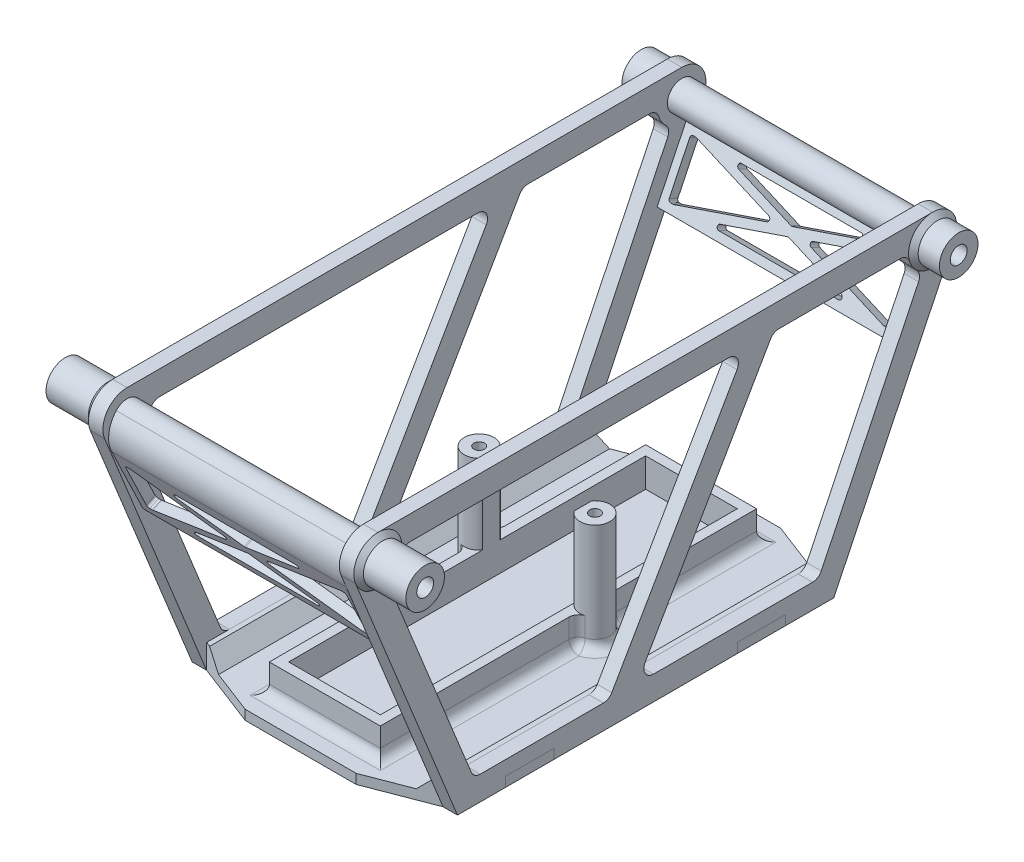
SolidWorks part; units mm, degrees
note: The reader was unsure of these and kept them because the rebuilt part matched: shared geometry of "Motor Box Sketch<3>", "Sketch6<3>".
other "Base Plate"
other "Left Wall"
other "Right Wall" parameters "Right Wall Plane"=27.5, "D5"=6.6366, "Joint Hole"=2.3, "D1"=14.5895, "D2"=39.8474, "D3"=19.0477, "D4"=55.6971, "D6"=33.5359, "D7"=45.542, "Wall Width"=5, "Notch Width"=10, "D8"=2.3856, "Notch Height"=2, "D9"=11.0795, "Bottom Notch From Edge"=10, "Screw Hole Diameter"=2.2, "Motor Box Length"=74, "Motor Box Width"=19, "Screw Hole Centre from Motor Rear"=20, "Screw Hole Spacing"=24, "Screw Hole Wall Thickness"=2, "Motor Rear to Shaft Centre"=12.5, "Motor Length"=74, "Motor Width"=19, "Motor Wall Thickness"=2, "IDK"=0, "Motor Shaft Above Base"=14, "Front Riser"=9.8, "Rear Riser"=5.4, "Edge Chamfer Width"=4
material "ABS"
ref_plane "Front Plane" through (0, 0, 0) normal (0, 0, 1) x (1, 0, 0)
ref_plane "Top Plane" through (0, 0, 0) normal (0, 1, 0) x (1, 0, 0)
ref_plane "Right Plane" through (0, 0, 0) normal (1, 0, 0) x (0, 0, -1)
sketch "Motor Box Sketch" plane through (0, 0, 0) normal (0, 1, 0) x (1, 0, 0)
  line L0 (-11.5, 14.5) -> (11.5, 14.5)
  line L1 (-9.5, -61.5) -> (9.5, -61.5)
  line L2 (-9.5, -61.5) -> (-9.5, 12.5)
  line L3 (-9.5, 12.5) -> (9.5, 12.5)
  line L4 (9.5, -61.5) -> (9.5, 12.5)
  line L5 (-9.5, -61.5) -> (9.5, 12.5) construction
  line L6 (-9.5, 12.5) -> (9.5, -61.5) construction
  line L7 (11.5, -63.5) -> (11.5, -22.5594)
  line L8 (-11.5, -63.5) -> (11.5, -63.5)
  line L9 (-11.5, -63.5) -> (-11.5, -22.5594)
  line L10 (-12, -19.5) -> (12, -19.5) construction
  line L11 (0, -24.5) -> (0, -19.5) construction
  line L12 (-11.5, -16.4406) -> (-11.5, 14.5)
  line L13 (-11.5, -63.5) -> (-11.5, 14.5) construction
  line L14 (11.5, -16.4406) -> (11.5, 14.5)
  line L15 (11.5, -63.5) -> (11.5, 14.5) construction
  line L16 (-9.5, -61.5) -> (-9.5, 12.5)
  line L17 (-9.5, -61.5) -> (9.5, -61.5)
  line L18 (-9.5, 12.5) -> (9.5, -61.5) construction
  circle A0 centre (-12, -19.5) radius 1.1
  circle A1 centre (12, -19.5) radius 1.1
  arc A2 (-11.5, -16.4406) -> (-11.5, -22.5594) centre (-12, -19.5) ccw
  arc A3 (11.5, -16.4406) -> (11.5, -22.5594) centre (12, -19.5) cw
  arc A6 (11.5, -16.4406) -> (11.5, -22.5594) centre (12, -19.5) ccw
  arc A8 (-11.5, -16.4406) -> (-11.5, -22.5594) centre (-12, -19.5) cw
  dimension "Screw Hole Centre from Motor Rear" = 19.5
extrude "Motor Box Extrude" add sketch "Motor Box Sketch" along normal blind 8 from offset 14 offset against normal yes
extrude "Motor Riser Extrude" add sketch "Motor Box Sketch<3>" along normal blind 24.5 from surface at -14 contours A3 A6 L4 A1 | A8 A2 L16 A0
sketch "Motor Box Sketch<3>" plane through (0, 0, 0) normal (0, 1, 0) x (1, 0, 0) same geometry as "Motor Box Sketch"
ref_plane "Right Wall" through (-27.5, 0, 0) normal (1, 0, 0) x (0, 0, -1)
sketch "Right Wall Sketch" plane through (-27.5, 0, 0) normal (1, 0, 0) x (0, 0, -1)
  line L0 (35, 45) -> (-80, 45)
  line L1 (22.0941, 13.2483) -> (26.5974, 11.0758) construction
  line L2 (32.8274, 35.4967) -> (11.3607, -9)
  line L3 (-17.9527, 15.5) -> (-13.6226, 13) construction
  line L6 (1.9658, 40) -> (30, 40)
  line L7 (14.5, -14) -> (4.5, -14)
  line L8 (14.5, -6) -> (14.5, -14) construction
  line L9 (-63.5, -6) -> (-63.5, -14) construction
  line L10 (-63.5, -14) -> (-84.6336, 38.1212)
  line L11 (14.5, -14) -> (39.5033, 37.8274)
  line L13 (11.3607, -9) -> (-26.3243, -9)
  line L14 (-26.3243, -9) -> (1.9658, 40)
  line L15 (-75, 40) -> (-3.8077, 40)
  line L17 (-60.132, -9) -> (-78.1212, 35.3664)
  line L18 (-69.1266, 13.1832) -> (-73.7602, 11.3044) construction
  line L19 (-24.5, -14) -> (-24.5, -9) construction
  line L20 (-5.5, -12) -> (-24.5, -12) construction
  line L24 (1.9658, 40) -> (-3.8077, 40) construction
  line L25 (-39.4038, 40) -> (-39.4038, 45) construction
  line L27 (4.5, -14) -> (4.5, -12)
  line L28 (4.5, -12) -> (-5.5, -12)
  line L29 (-5.5, -12) -> (-5.5, -14)
  line L30 (-43.5, -14) -> (-43.5, -12)
  line L31 (-43.5, -12) -> (-53.5, -12)
  line L32 (-53.5, -12) -> (-53.5, -14)
  line L33 (-24.5, -12) -> (-43.5, -12) construction
  line L34 (-5.5, -14) -> (-43.5, -14)
  line L35 (-53.5, -14) -> (-63.5, -14)
  line L36 (-60.132, -9) -> (-32.0978, -9)
  line L37 (-22.6, -14) -> (-16.4, -14) construction
  line L38 (-32.0978, -9) -> (-3.8077, 40)
  line L39 (-16.4406, -14) -> (14.5, -14) construction
  circle A0 centre (35, 40) radius 1.15
  circle A1 centre (-80, 40) radius 1.15
  arc A2 (39.5033, 37.8274) -> (35, 45) centre (35, 40) ccw
  arc A3 (-80, 45) -> (-84.6336, 38.1212) centre (-80, 40) ccw
  arc A4 (-75, 40) -> (-78.1212, 35.3664) centre (-80, 40) cw
  arc A5 (30, 40) -> (32.8274, 35.4967) centre (35, 40) ccw
  arc A6 (39.5033, 37.8274) -> (32.8274, 35.4967) centre (35, 40) cw construction
  arc A7 (-84.6336, 38.1212) -> (-78.1212, 35.3664) centre (-80, 40) ccw construction
  point P54 (-17.9527, 15.5)
  dimension "D1" = 35
  dimension "D2" = 40
  dimension "D3" = 40
  dimension "D4" = 80
  dimension "D6" = 60
  dimension "D7" = 2
extrude "Right Wall Extrude" add sketch "Right Wall Sketch" along normal blind 3 separate body
sketch "Sketch6" plane through (-27.5, 0, 0) normal (-1, 0, 0) x (0, 0, 1)
  circle A0 centre (-35, 40) radius 4
  circle A1 centre (80, 40) radius 4
  circle A3 centre (-35, 40) radius 1.75
  circle A4 centre (80, 40) radius 1.75
  circle M24 centre (-35, 40) radius 1.15
  circle M25 centre (80, 40) radius 1.15
  dimension "D1" = 2.25
  dimension "Threaded Insert Hole" = 3.5
extrude "Front Joint Riser Extrude" add sketch "Sketch6" along normal blind 9.8 contours A1 M25
extrude "Rear Joint Riser Extrude" add sketch "Sketch6<3>" along normal blind 5.4 contours A0 M24
sketch "Sketch6<3>" plane through (-27.5, 0, 0) normal (-1, 0, 0) x (0, 0, 1) same geometry as "Sketch6"
fillet "Right Wall Fillet" radius 2 10 edges at (-26, 35.3664, 78.1212) (-26, 40, 75) (-26, 40, -1.9658) (-26, 35.4967, -32.8274) (-26, 40, -30) (-26, -9, -11.3607) (-26, -9, 26.3243) (-26, 40, 3.8077) (-26, -9, 60.132) (-26, -9, 32.0978)
chamfer "Riser Fillet" distance 1 angle 45 2 edges at (-27.5, 40, 76) (-27.5, 40, -39)
mirror "Left Wall Mirror" about plane through (0, 0, 0) normal (1, 0, 0) of bodies 107 102
sketch "Bottom Plate Sketch" plane through (0, -14, 0) normal (0, -1, 0) x (1, 0, 0)
  line L12 (24.5, -4.5) -> (24.5, -14.5) construction
  line L13 (24.5, -4.5) -> (27.5, -4.5) construction
  line L14 (27.5, 5.5) -> (27.5, -4.5) construction
  line L15 (24.5, 5.5) -> (27.5, 5.5) construction
  line L16 (24.5, 43.5) -> (24.5, 5.5) construction
  line L17 (24.5, 43.5) -> (27.5, 43.5) construction
  line L18 (27.5, 53.5) -> (27.5, 43.5) construction
  line L19 (24.5, 53.5) -> (27.5, 53.5) construction
  line L20 (24.5, 63.5) -> (24.5, 53.5) construction
  line L21 (-24.5, 63.5) -> (-24.5, 53.5) construction
  line L22 (-24.5, 53.5) -> (-27.5, 53.5) construction
  line L23 (-27.5, 53.5) -> (-27.5, 43.5) construction
  line L24 (-24.5, 43.5) -> (-27.5, 43.5) construction
  line L25 (-24.5, 43.5) -> (-24.5, 5.5) construction
  line L26 (-24.5, 5.5) -> (-27.5, 5.5) construction
  line L27 (-27.5, 5.5) -> (-27.5, -4.5) construction
  line L28 (-24.5, -4.5) -> (-27.5, -4.5) construction
  line L29 (-24.5, -4.5) -> (-24.5, -14.5) construction
  line L30 (24.5, -4.5) -> (24.5, -14.5)
  line L31 (24.5, -4.5) -> (27.5, -4.5)
  line L32 (27.5, 5.5) -> (27.5, -4.5)
  line L33 (24.5, 5.5) -> (27.5, 5.5)
  line L34 (24.5, 43.5) -> (24.5, 5.5)
  line L35 (24.5, 43.5) -> (27.5, 43.5)
  line L36 (27.5, 53.5) -> (27.5, 43.5)
  line L37 (24.5, 53.5) -> (27.5, 53.5)
  line L38 (24.5, 63.5) -> (24.5, 53.5)
  line L39 (-24.5, 63.5) -> (-24.5, 53.5)
  line L40 (-24.5, 53.5) -> (-27.5, 53.5)
  line L41 (-27.5, 53.5) -> (-27.5, 43.5)
  line L42 (-24.5, 43.5) -> (-27.5, 43.5)
  line L43 (-24.5, 43.5) -> (-24.5, 5.5)
  line L44 (-24.5, 5.5) -> (-27.5, 5.5)
  line L45 (-27.5, 5.5) -> (-27.5, -4.5)
  line L46 (-24.5, -4.5) -> (-27.5, -4.5)
  line L47 (-24.5, -4.5) -> (-24.5, -14.5)
  line L48 (-24.5, 63.5) -> (-11.5, 68.5)
  line L49 (-11.5, 68.5) -> (11.5, 68.5)
  line L50 (11.5, 68.5) -> (24.5, 63.5)
  line L51 (-24.5, -14.5) -> (-11.5, -19.5)
  line L52 (-11.5, -19.5) -> (11.5, -19.5)
  line L53 (11.5, -19.5) -> (24.5, -14.5)
  line L54 (0, 63.5) -> (0, 68.5) construction
  line L55 (0, -19.5) -> (0, -14.5) construction
  line L56 (-11.5, -14.5) -> (11.5, -14.5) construction
  line L57 (-11.5, 63.5) -> (11.5, 63.5) construction
  line L58 (-11.5, -14.5) -> (11.5, -14.5) construction
  line L59 (-11.5, 63.5) -> (11.5, 63.5) construction
  dimension "D1" = 5
extrude "Bottom Plate Extrude" add sketch "Bottom Plate Sketch" against normal blind 2
fillet "Box Fillet" radius 2 12 edges at (11.5, -9, 16.4406) (11.5, -9, 22.5594) (-11.5, -9, 22.5594) (-11.5, -9, 16.4406) (-11.5, -12, 0.9703) (0, -12, -14.5) (11.5, -12, 0.9703) (15.1, -12, 19.5) (-15.1, -12, 19.5) (-11.5, -12, 43.0297) (11.5, -12, 43.0297) (0, -12, 63.5)
sketch "Sketch7" plane through (0, -12, 0) normal (0, 1, 0) x (1, 0, 0)
  line L0 (-20.5, 16.0385) -> (-20.5, -65.0385)
  line L1 (-24.5, 14.5) -> (-11.5, 19.5) construction
  line L2 (-11.5, -68.5) -> (-24.5, -63.5) construction
  line L3 (20.5, -65.0385) -> (20.5, 16.0385)
  line L4 (24.5, -63.5) -> (11.5, -68.5) construction
  line L5 (11.5, 19.5) -> (24.5, 14.5) construction
  line L6 (-24.5, -43.5) -> (-24.5, -5.5) construction
  line L7 (20.5, -24.5) -> (24.5, -24.5) construction
  line L8 (24.5, -5.5) -> (24.5, -43.5) construction
  line L9 (-20.5, -24.5) -> (-24.5, -24.5) construction
  line L10 (20.5, 16.0385) -> (24.5, 14.5)
  line L11 (24.5, -63.5) -> (11.5, -68.5)
  line L12 (-11.5, -68.5) -> (-24.5, -63.5)
  line L13 (-24.5, 14.5) -> (-20.5, 16.0385)
  line L14 (-24.5, 14.5) -> (-24.5, -63.5)
  line L15 (24.5, 14.5) -> (24.5, -63.5)
  line M13 (24.5, 4.5) -> (24.5, 14.5)
  line M14 (24.5, 14.5) -> (11.5, 19.5)
  line M16 (-11.5, 19.5) -> (-24.5, 14.5)
  line M17 (-24.5, 14.5) -> (-24.5, 4.5)
  line M21 (-24.5, -5.5) -> (-24.5, -43.5)
  line M25 (-24.5, -53.5) -> (-24.5, -63.5)
  line M26 (-24.5, -63.5) -> (-11.5, -68.5)
  line M28 (11.5, -68.5) -> (24.5, -63.5)
  line M29 (24.5, -63.5) -> (24.5, -53.5)
  line M33 (24.5, -43.5) -> (24.5, -5.5)
extrude "Base Plate Chamfer Extrude" add sketch "Sketch7" along normal blind 3 contours L15 L3 M13 M14 M28 M29 M33 | L14 L0 M17 M21 M25 M26 M16
chamfer "Base Plate Chamfer" distance 3 angle 45 2 edges at (-20.5, -9, 24.5) (20.5, -9, 24.5)
sketch "Sketch8" plane through (-24.5, 0, 0) normal (1, 0, 0) x (0, 0, -1)
  line L0 (14.5, -14) -> (39.5033, 37.8274) construction
  line L2 (31.6821, 21.6155) -> (38.1998, 35.1254)
  line L3 (29.8808, 22.4845) -> (36.3985, 35.9945)
  line L4 (31.6821, 21.6155) -> (29.8808, 22.4845)
  line L6 (36.3985, 35.9945) -> (33.6965, 37.298)
  line L7 (36.3985, 35.9945) -> (38.1998, 35.1254) construction
  circle A0 centre (35, 40) radius 1.15 construction
  circle A2 centre (35, 40) radius 1.15
  arc A5 (37.2425, 41.9928) -> (33.6965, 37.298) centre (35, 40) ccw
  arc A6 (38.1998, 35.1254) -> (37.2425, 41.9928) centre (32.5706, 37.8411) ccw
  circle M4 centre (35, 40) radius 1.15
  line M18 (14.5, -14) -> (39.5033, 37.8274)
  dimension "D2" = 15
  dimension "D3" = 3
  dimension "D1" = 2
extrude "Boss-Extrude1" add sketch "Sketch8" along direction (-1, 0, 0) on the side of the normal up to surface (49 mm away) separate body contours L6 L7 A6 A5 M4 | L7 L3 L4 M18 up to face at (24.5, 40, -36.15)
fillet "Fillet1" radius 1 1 edges at (0, 35.9945, -36.3985)
sketch "Sketch9" plane through (0, -7.4488, -15.44) normal (0, 0.4345, 0.9007) x (1, 0, 0)
  line L0 (24.2802, 48.0038) -> (-25.6127, 33.7487) construction
  line L1 (24.7198, 46.4653) -> (-25.1731, 32.2102) construction
  line L2 (-24.2802, 48.0038) -> (25.9696, 33.6467) construction
  line L3 (-24.7198, 46.4653) -> (25.53, 32.1083) construction
  line L9 (15.988, 45.6346) -> (-15.988, 45.6346)
  line L11 (-22.9, 34.8346) -> (-22.9, 45.6346)
  line L20 (-24.5, 47.2346) -> (24.5, 33.2346) construction
  line L21 (24.5, 47.2346) -> (-24.5, 33.2346) construction
  line L22 (-21.812, 45.6346) -> (-2.912, 40.2346)
  line L23 (15.988, 45.6346) -> (0, 41.0666)
  line L24 (-15.988, 45.6346) -> (0, 41.0666)
  line L25 (21.812, 45.6346) -> (2.912, 40.2346)
  line L30 (0, 39.4026) -> (15.988, 34.8346)
  line L31 (2.912, 40.2346) -> (21.812, 34.8346)
  line L32 (0, 39.4026) -> (-15.988, 34.8346)
  line L33 (-2.912, 40.2346) -> (-21.812, 34.8346)
  line L34 (21.812, 45.6346) -> (22.9, 45.6346)
  line L35 (24.5, 47.2346) -> (-24.5, 47.2346) construction
  line L36 (24.5, 47.2346) -> (-24.5, 47.2346)
  line L37 (-24.5, 33.2346) -> (-24.5, 47.2346) construction
  line L38 (24.5, 33.2346) -> (-24.5, 33.2346) construction
  line L39 (24.5, 47.2346) -> (24.5, 33.2346) construction
  line L40 (-24.5, 33.2346) -> (-24.5, 47.2346)
  line L41 (24.5, 33.2346) -> (-24.5, 33.2346)
  line L42 (24.5, 47.2346) -> (24.5, 33.2346)
  line L43 (24.5, 47.2346) -> (-25.3929, 32.9795) construction
  line L44 (-24.5, 47.2346) -> (25.7498, 32.8775) construction
  line L45 (22.9, 34.8346) -> (21.812, 34.8346)
  line L46 (22.9, 45.6346) -> (22.9, 34.8346)
  line L47 (-21.812, 45.6346) -> (-22.9, 45.6346)
  line L48 (22.9, 45.6346) -> (-22.9, 45.6346) construction
  line L49 (-21.812, 34.8346) -> (-22.9, 34.8346)
  line L50 (22.9, 34.8346) -> (-22.9, 34.8346) construction
  line L51 (15.988, 34.8346) -> (-15.988, 34.8346)
  dimension "D1" = 1.6
  dimension "D2" = 0.8
  dimension "D3" = 0.8
extrude "Cut-Extrude1" cut sketch "Sketch9" against normal blind 10
fillet "Fillet2" radius 0.5 15 edges at (0, 27.6053, -33.4615) (2.912, 28.3546, -33.823) (15.988, 23.491, -31.4767) (21.812, 23.491, -31.4767) (22.9, 23.491, -31.4767) (0, 29.104, -34.1846) (22.9, 33.2182, -36.1694) (15.988, 33.2182, -36.1694) (-15.988, 33.2182, -36.1694) (-15.988, 23.491, -31.4767) (-2.912, 28.3546, -33.823) (-21.812, 23.491, -31.4767) (-22.9, 23.491, -31.4767) (-21.812, 33.2182, -36.1694) (-22.9, 33.2182, -36.1694)
sketch "Sketch10" plane through (0, 0, 0) normal (1, 0, 0) x (0, 0, -1)
  line L0 (35, 40) -> (-80, 40) construction
  circle A0 centre (35, 40) radius 1.15 construction
  circle A1 centre (-80, 40) radius 1.15 construction
  circle A2 centre (35, 40) radius 1.15 construction
  circle A3 centre (-80, 40) radius 1.15 construction
  point P6 (-22.5, 40)
ref_plane "Plane1" through (0, 0, 22.5) normal (0, 0, 1) x (1, 0, 0)
mirror "Mirror1" about plane through (0, 0, 22.5) normal (0, 0, 1) of bodies 114
equation "\"Overall Width\"= 55"
equation "\"Rear Ground X\"= 35"
equation "\"Rear Ground Y\"= 40"
equation "\"Front Ground X\"= 80"
equation "\"Front Ground Y\"= 40"
equation "\"Right Wall Plane@Right Wall\" = \"Overall Width\" / 2"
equation "\"D1@Right Wall Sketch\" = \"Rear Ground X\""
equation "\"D2@Right Wall Sketch\" = \"Rear Ground Y\""
equation "\"D3@Right Wall Sketch\" = \"Front Ground Y\""
equation "\"D4@Right Wall Sketch\" = \"Front Ground X\""
equation "\"Joint Hole Diameter\"= 2.3"
equation "\"Joint Hole@Right Wall Sketch\" = \"Joint Hole Diameter\""
equation "\"Notch Width\"=10"
equation "\"Notch Height\"=2"
equation "\"Bottom Notch From Edge@Right Wall Sketch\" = \"Notch Width\""
equation "\"D1@Bottom Plate Extrude\" = \"Notch Height\""
equation "\"Motor Shaft Height\"= 12"
equation "\"Motor Shaft from End\"= 12.5"
equation "\"Motor Rear to Shaft Centre@Motor Box Sketch\"= \"Motor Shaft from End\""
equation "\"Motor Shaft Above Base@Motor Box Extrude\"= \"Motor Shaft Height\" + \"Base Plate Thickness\""
equation "\"Motor Riser Height\"= 22.5"
equation "\"D1@Motor Riser Extrude\" = \"Motor Riser Height\" + \"Base Plate Thickness\""
equation "\"Base Plate Thickness\"= 2"
equation "\"Screw Hole from Shaft\"= 19.5"
equation "\"Screw Hole Centre from Motor Rear@Motor Box Sketch\"=\"Screw Hole from Shaft\""
equation "\"Front Linkage Riser\"= 9.8"
equation "\"Rear Linkage Riser\"= 5.4"
equation "\"Front Riser@Front Joint Riser Extrude\"= \"Front Linkage Riser\""
equation "\"Rear Riser@Rear Joint Riser Extrude\"= \"Rear Linkage Riser\""
equation "\"D7@Right Wall Sketch\"=\"Notch Height\""
equation "\"Base Plate Edge Chamfer Height\"= 3"
equation "\"Edge Chamfer Width@Sketch7\" = \"Base Plate Edge Chamfer Height\" + 1"
equation "\"D1@Base Plate Chamfer Extrude\" = \"Base Plate Edge Chamfer Height\""
equation "\"D3@LPattern1\"=\"Rear Ground X\"+\"Front Ground X\""
